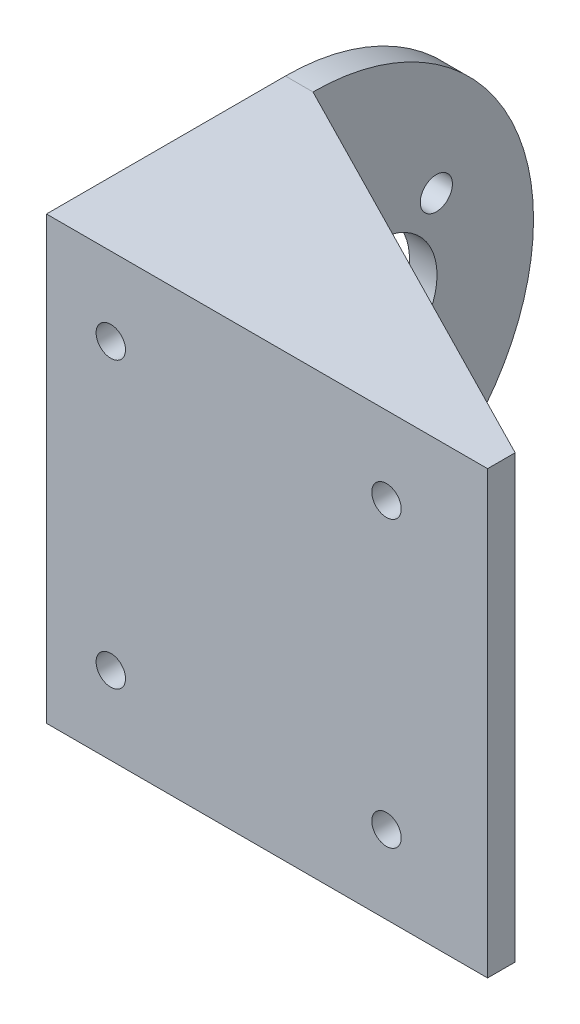
SolidWorks part; units mm, degrees
ref_plane "Front Plane" through (0, 0, 0) normal (0, 0, 1) x (1, 0, 0)
ref_plane "Top Plane" through (0, 0, 0) normal (0, 1, 0) x (1, 0, 0)
ref_plane "Right Plane" through (0, 0, 0) normal (1, 0, 0) x (0, 0, -1)
sketch "Sketch1" plane through (0, 0, 0) normal (0, 0, 1) x (1, 0, 0)
  line L0 (4, 8.5) -> (4, 39.5) construction
  line L1 (0, 0) -> (45, 0)
  line L2 (0, 0) -> (0, 48)
  line L3 (0, 48) -> (45, 48)
  line L4 (45, 0) -> (45, 48)
  circle A0 centre (4, 8.5) radius 1.6
  circle A1 centre (4, 39.5) radius 1.6
  circle A2 centre (34, 8.5) radius 1.6
  circle A3 centre (34, 39.5) radius 1.6
  point P13 (4, 24)
  point P14 (0, 24)
  dimension "D4" = 3.2
  dimension "D1" = 31
  dimension "D2" = 30
  dimension "D3" = 48
  dimension "D5" = 4
  dimension "D6" = 45
extrude "Boss-Extrude1" add sketch "Sketch1" along normal blind 3
sketch "Sketch2" plane through (0, 0, 0) normal (-1, 0, 0) x (0, 0, 1)
  line L0 (3, 48) -> (-23, 48)
  line L1 (3, 48) -> (3, 0)
  line L2 (3, 0) -> (-23, 0)
  arc A0 (-23, 0) -> (-23, 48) centre (-23, 24) cw
  point P8 (-47, 24)
  dimension "D1" = 50
extrude "Boss-Extrude2" add sketch "Sketch2" along normal blind 3
sketch "Sketch4" plane through (-3, 0, 0) normal (-1, 0, 0) x (0, 0, 1)
  circle A0 centre (-30, 24) radius 6.5
  circle A4 centre (-23, 24) radius 15.5 construction
  arc A5 (-23, 48) -> (-23, 0) centre (-23, 24) ccw construction
  circle A6 centre (-23, 39.5) radius 1.75
  circle A7 centre (-9.5766, 31.75) radius 1.75
  circle A8 centre (-9.5766, 16.25) radius 1.75
  circle A9 centre (-23, 8.5) radius 1.75
  circle A10 centre (-36.4234, 16.25) radius 1.75
  circle A11 centre (-36.4234, 31.75) radius 1.75
  point P17 (-47, 24)
  dimension "D1" = 3.5
  dimension "D2" = 13
  dimension "D3" = 31
  dimension "D5" = 7
  dimension "D4" = 6
extrude "Cut-Extrude1" cut sketch "Sketch4" against normal blind 10
sketch "Sketch5" plane through (0, 48, 0) normal (0, 1, 0) x (1, 0, 0)
  line L0 (0, 23) -> (45, 0)
  line L1 (0, 23) -> (0, 0)
  line L2 (0, 0) -> (45, 0)
extrude "Boss-Extrude3" add sketch "Sketch5" against normal blind 3
extrude "Boss-Extrude4" add sketch "Sketch5<2>" along normal blind 3 from surface starting at face at (14, 0, -6.6667)
sketch "Sketch5<2>" plane through (0, 48, 0) normal (0, 1, 0) x (1, 0, 0) same geometry as "Sketch5"
